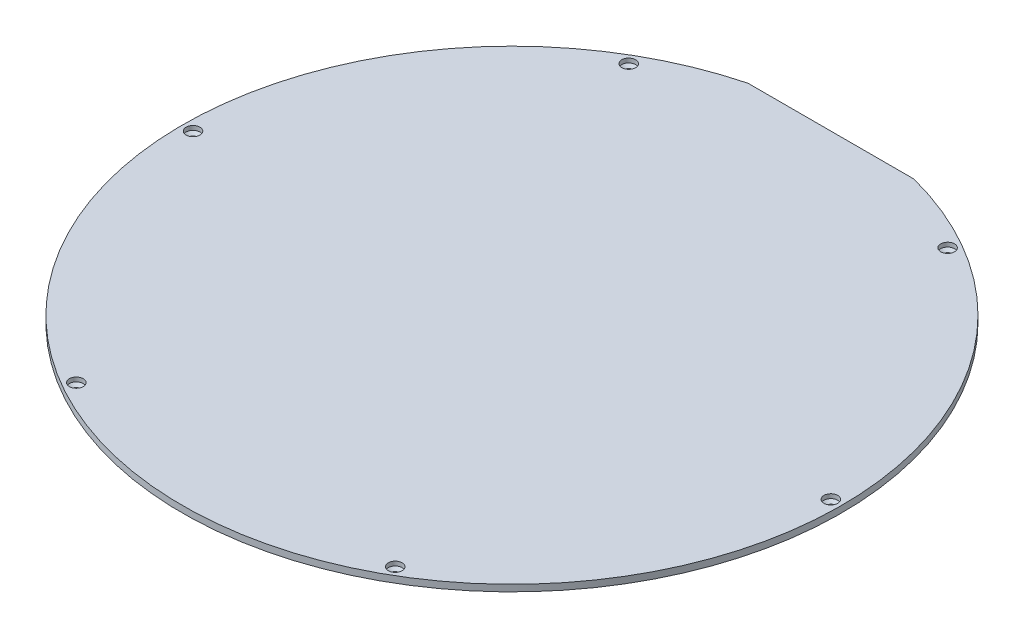
SolidWorks part; units mm, degrees
ref_plane "Front Plane" through (0, 0, 0) normal (0, 0, 1) x (1, 0, 0)
ref_plane "Top Plane" through (0, 0, 0) normal (0, 1, 0) x (1, 0, 0)
ref_plane "Right Plane" through (0, 0, 0) normal (1, 0, 0) x (0, 0, -1)
sketch "Sketch1" plane through (0, 0, 0) normal (0, 1, 0) x (1, 0, 0)
  circle A0 centre (0, 0) radius 155
  dimension "D1" = 310
extrude "Boss-Extrude1" add sketch "Sketch1" along normal blind 3.1
sketch "Sketch2" plane through (0, 3.1, 0) normal (0, 1, 0) x (1, 0, 0)
  line L0 (0, 0) -> (150, 0) construction
  circle A1 centre (150, 0) radius 1.65
  circle A2 centre (0, 0) radius 150
  circle A3 centre (0, 0) radius 150 construction
  dimension "D2" = 3.3
  dimension "D1" = 5
extrude "Cut-Extrude1" cut sketch "Sketch2" against normal through all
sketch "Sketch3" plane through (0, 3.1, 0) normal (0, 1, 0) x (1, 0, 0)
  circle A0 centre (150, 0) radius 3.25
  dimension "D1" = 6.5
extrude "Cut-Extrude2" cut sketch "Sketch3" against normal blind 2
chamfer "Chamfer1" distance 1.1 distance2 1.6 1 edges at (150, 1.1, 1.65) first distance on face at (150, 0, 1.65)
pattern_circular "CirPattern1" count 6 over 360 about axis through (0, 3.1, 0) along (0, -1, 0) of "Cut-Extrude1", "Cut-Extrude2", "Chamfer1"
sketch "Sketch4" plane through (0, 3.1, 0) normal (0, 1, 0) x (1, 0, 0)
  line L0 (-150, 0) -> (150, 0) construction
  line L1 (75, 129.9038) -> (-75, -129.9038) construction
  line L2 (75, -129.9038) -> (-75, 129.9038) construction
  line L3 (0, 0) -> (0, 155) construction
  line L4 (0, 150.0133) -> (39, 150.0133)
  line L5 (0, 150.0133) -> (-39, 150.0133)
  circle A1 centre (0, 0) radius 155 construction
  arc A2 (-39, 150.0133) -> (39, 150.0133) centre (0, 0) cw
  dimension "D1" = 78
extrude "Cut-Extrude3" cut sketch "Sketch4" against normal through all
